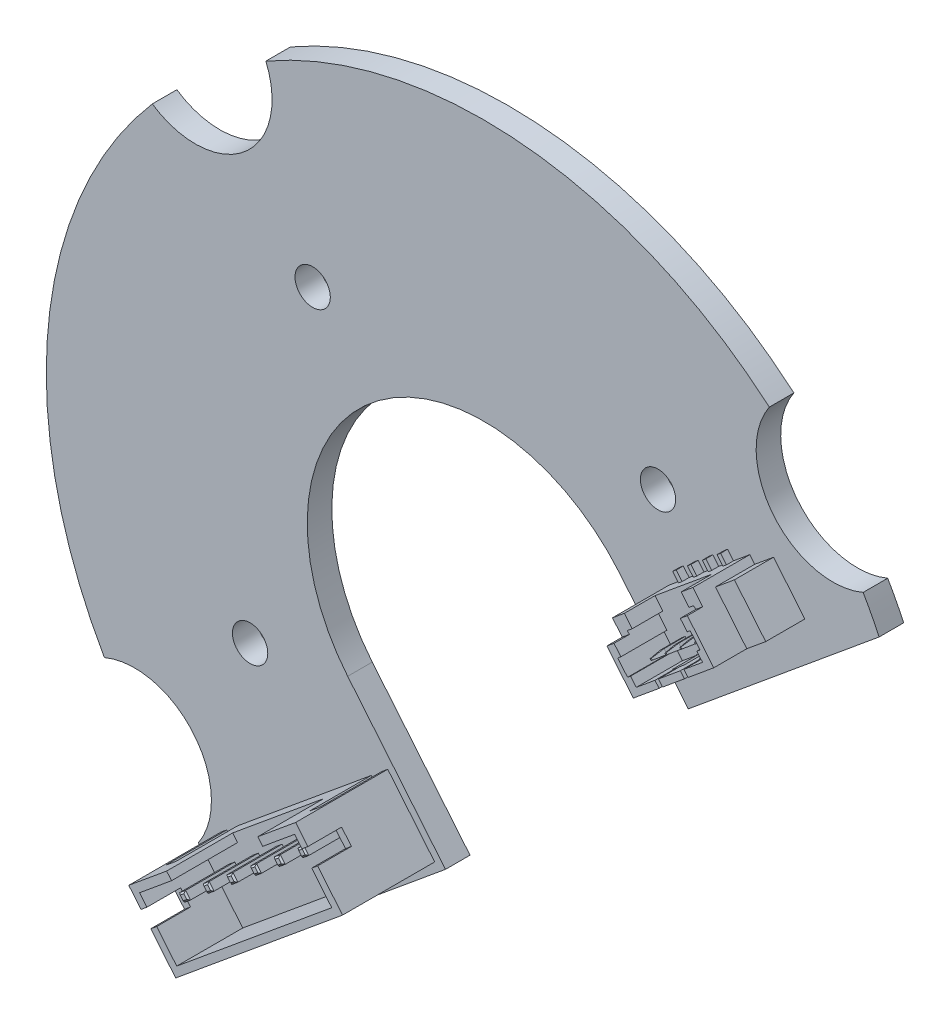
SolidWorks part; units mm, degrees
ref_plane "前视基准面" through (0, 0, 0) normal (0, 0, 1) x (1, 0, 0)
ref_plane "上视基准面" through (0, 0, 0) normal (0, 1, 0) x (1, 0, 0)
ref_plane "右视基准面" through (0, 0, 0) normal (1, 0, 0) x (0, 0, -1)
sketch "草图2" plane through (0, 0, 0) normal (0, 0, 1) x (1, 0, 0)
  line L0 (-14.2036, -24.7084) -> (-2.4954, -15.0341)
  line L1 (-8.8652, -7.3252) -> (-2.4954, -15.0341)
  line L2 (8.8652, 7.3252) -> (13.324, 1.929)
  line L3 (25.756, 12.2015) -> (13.324, 1.929)
  arc A0 (-18.6004, -21.5934) -> (-14.2036, -24.7084) centre (0, 0) ccw
  arc A1 (-21.5934, 18.6004) -> (-14.196, 24.7128) centre (-18.7908, 22.7411) ccw
  arc A2 (-18.6004, -21.5934) -> (-24.7128, -14.196) centre (-22.7411, -18.7908) ccw
  arc A3 (18.6004, 21.5934) -> (24.7128, 14.196) centre (22.7411, 18.7908) ccw
  arc A4 (8.8652, 7.3252) -> (-8.8652, -7.3252) centre (0, 0) ccw
  arc A5 (25.756, 12.2015) -> (24.7128, 14.196) centre (0, 0) ccw
  arc A6 (-21.5934, 18.6004) -> (-24.7128, -14.196) centre (0, 0) ccw
  arc A7 (18.6004, 21.5934) -> (-14.196, 24.7128) centre (0, 0) ccw
  dimension "D1" = 57
  dimension "D2" = 10
  dimension "D3" = 10
  dimension "D4" = 10
  dimension "D5" = 23
  dimension "D6" = 10
  dimension "D7" = 7
extrude "凸台-拉伸1" add sketch "草图2" along normal blind 1.6
sketch "草图3" plane through (0, 0, 1.6) normal (0, 0, 1) x (1, 0, 0)
  line L0 (-6.2568, -11.2669) -> (-3.1994, -14.9671)
  line L1 (-3.1994, -14.9671) -> (-14.0688, -23.9484)
  line L2 (-14.0688, -23.9484) -> (-17.1263, -20.2482)
  line L3 (-17.1263, -20.2482) -> (-6.2568, -11.2669)
  line L6 (-2.4954, -15.0341) -> (-8.8652, -7.3252) construction
  line L8 (-14.2036, -24.7084) -> (-2.4954, -15.0341) construction
  dimension "D1" = 14.1
  dimension "D2" = 4.8
  dimension "D3" = 0.5
  dimension "D4" = 0.5
extrude "凸台-拉伸2" add sketch "草图3" along normal blind 6
sketch "草图4" plane through (0, 0, 7.6) normal (0, 0, 1) x (1, 0, 0)
  line L0 (-6.3238, -11.9708) -> (-3.9033, -14.9001)
  line L1 (-3.9033, -14.9001) -> (-14.0019, -23.2445)
  line L2 (-14.0019, -23.2445) -> (-16.4224, -20.3152)
  line L3 (-16.4224, -20.3152) -> (-14.341, -18.5953)
  line L4 (-3.1994, -14.9671) -> (-6.2568, -11.2669) construction
  line L5 (-17.1263, -20.2482) -> (-14.0688, -23.9484) construction
  line L6 (-6.2568, -11.2669) -> (-17.1263, -20.2482) construction
  line L7 (-14.0688, -23.9484) -> (-3.1994, -14.9671) construction
  line L8 (-7.2854, -21.09) -> (-12.9337, -14.2542) construction
  line L9 (-8.4029, -13.6887) -> (-8.7214, -13.3033)
  line L10 (-8.7214, -13.3033) -> (-14.6595, -18.2099)
  line L11 (-14.6595, -18.2099) -> (-14.341, -18.5953)
  line L12 (-8.4029, -13.6887) -> (-6.3238, -11.9708)
  dimension "D1" = 0.5
  dimension "D2" = 0.5
  dimension "D3" = 0.5
  dimension "D4" = 0.5
  dimension "D5" = 3.853
  dimension "D6" = 3.85
extrude "切除-拉伸1" cut sketch "草图4" against normal offset from surface (4.3 mm away) 1.7 up to face at (-1.9351, 2.4515, 1.6)
sketch "草图5" plane through (0, 0, 7.6) normal (0, 0, 1) x (1, 0, 0)
  line L0 (-5.8461, -12.5489) -> (-5.4606, -12.2305)
  line L1 (-3.9033, -14.9001) -> (-6.3238, -11.9708) construction
  line L2 (-3.1994, -14.9671) -> (-6.2568, -11.2669) construction
  line L3 (-5.4606, -12.2305) -> (-4.8236, -13.0013)
  line L4 (-4.8236, -13.0013) -> (-5.2091, -13.3198)
  line L5 (-5.2091, -13.3198) -> (-5.8461, -12.5489)
  line L6 (-15.9446, -20.8933) -> (-16.3301, -21.2118)
  line L7 (-16.4224, -20.3152) -> (-14.0019, -23.2445) construction
  line L8 (-17.1263, -20.2482) -> (-14.0688, -23.9484) construction
  line L9 (-16.3301, -21.2118) -> (-15.6931, -21.9827)
  line L10 (-15.6931, -21.9827) -> (-15.3077, -21.6642)
  line L11 (-15.3077, -21.6642) -> (-15.9446, -20.8933)
  line L12 (-14.6595, -18.2099) -> (-17.1263, -20.2482) construction
  line L13 (-6.2568, -11.2669) -> (-8.7214, -13.3033) construction
  dimension "D1" = 1.25
  dimension "D2" = 1
  dimension "D3" = 1.25
  dimension "D4" = 1
extrude "切除-拉伸2" cut sketch "草图5" against normal blind 2.2
sketch "草图6" plane through (2.9938, -3.6232, 0) normal (-0.637, 0.7709, 0) x (0.7709, 0.637, 0)
  line L0 (-28.0932, -1.6) -> (-4.798, -1.6) construction
  line L1 (-12.5, -5.6) -> (-13.4, -5.6)
  line L2 (-12.5, -5.6) -> (-12.5, -1.6)
  line L3 (-12.5, -1.6) -> (-13.4, -1.6)
  line L4 (-13.4, -5.6) -> (-13.4, -1.6)
  line L5 (-12, -7.6) -> (-12, -1.6) construction
  line L6 (-24.7, -5.6) -> (-25.6, -5.6)
  line L7 (-24.7, -5.6) -> (-24.7, -1.6)
  line L8 (-24.7, -1.6) -> (-25.6, -1.6)
  line L9 (-25.6, -5.6) -> (-25.6, -1.6)
  line L10 (-26.1, -7.6) -> (-26.1, -1.6) construction
  dimension "D1" = 0.5
  dimension "D2" = 0.5
  dimension "D3" = 0.9
  dimension "D4" = 0.9
  dimension "D5" = 4
  dimension "D6" = 4
extrude "切除-拉伸3" cut sketch "草图6" against normal blind 0.5
sketch "草图7" plane through (0, 0, 3.3) normal (0, 0, 1) x (1, 0, 0)
  line L0 (-6.8164, -13.4156) -> (-6.4979, -13.801)
  line L1 (-6.4979, -13.801) -> (-6.8833, -14.1195)
  line L2 (-6.8833, -14.1195) -> (-7.2018, -13.734)
  line L3 (-7.2018, -13.734) -> (-6.8164, -13.4156)
  line L5 (-6.2568, -11.2669) -> (-8.7214, -13.3033) construction
  line L6 (-3.1994, -14.9671) -> (-4.8236, -13.0013) construction
  line L7 (-8.4251, -15.3934) -> (-8.7436, -15.008)
  line L8 (-8.7436, -15.008) -> (-8.3581, -14.6895)
  line L9 (-8.3581, -14.6895) -> (-8.0396, -15.075)
  line L10 (-8.0396, -15.075) -> (-8.4251, -15.3934)
  line L11 (-9.9669, -16.6674) -> (-10.2853, -16.2819)
  line L12 (-10.2853, -16.2819) -> (-9.8999, -15.9635)
  line L13 (-9.8999, -15.9635) -> (-9.5814, -16.3489)
  line L14 (-9.5814, -16.3489) -> (-9.9669, -16.6674)
  line L15 (-11.5086, -17.9413) -> (-11.8271, -17.5559)
  line L16 (-11.8271, -17.5559) -> (-11.4417, -17.2374)
  line L17 (-11.4417, -17.2374) -> (-11.1232, -17.6229)
  line L18 (-11.1232, -17.6229) -> (-11.5086, -17.9413)
  line L19 (-13.0504, -19.2153) -> (-13.3689, -18.8298)
  line L20 (-13.3689, -18.8298) -> (-12.9834, -18.5114)
  line L21 (-12.9834, -18.5114) -> (-12.6649, -18.8968)
  line L22 (-12.6649, -18.8968) -> (-13.0504, -19.2153)
  line L23 (-14.5922, -20.4892) -> (-14.9106, -20.1038)
  line L24 (-14.9106, -20.1038) -> (-14.5252, -19.7853)
  line L25 (-14.5252, -19.7853) -> (-14.2067, -20.1708)
  line L26 (-14.2067, -20.1708) -> (-14.5922, -20.4892)
  dimension "D1" = 1.8
  dimension "D2" = 0.5
  dimension "D3" = 0.5
  dimension "D4" = 2.3
  dimension "D5" = 6
extrude "凸台-拉伸3" add sketch "草图7" along normal blind 3.3
extrude "凸台-拉伸4" add sketch "草图7<3>" against normal offset from surface (4.4 mm away) 2.7 up to face at (-1.9351, 2.4515, 1.6)
sketch "草图7<3>" plane through (0, 0, 3.3) normal (0, 0, 1) x (1, 0, 0) same geometry as "草图7"
chamfer "倒角1" distance 0.1 angle 45 24 edges at (-14.3994, -20.33, 6.6) (-14.7514, -20.2965, 6.6) (-14.7179, -19.9446, 6.6) (-14.366, -19.978, 6.6) (-12.8577, -19.056, 6.6) (-13.2096, -19.0226, 6.6) (-13.1762, -18.6706, 6.6) (-12.8242, -18.7041, 6.6) (-11.3159, -17.7821, 6.6) (-11.6679, -17.7486, 6.6) (-11.6344, -17.3967, 6.6) (-11.2824, -17.4301, 6.6) (-9.7741, -16.5081, 6.6) (-10.1261, -16.4747, 6.6) (-10.0926, -16.1227, 6.6) (-9.7407, -16.1562, 6.6) (-6.6571, -13.6083, 6.6) (-6.6906, -13.9602, 6.6) (-7.0426, -13.9268, 6.6) (-7.0091, -13.5748, 6.6) (-8.2324, -15.2342, 6.6) (-8.5843, -15.2007, 6.6) (-8.5508, -14.8488, 6.6) (-8.1989, -14.8822, 6.6)
chamfer "倒角2" distance 0.1 angle 45 24 edges at (-14.7179, -19.9446, -1.1) (-14.7514, -20.2965, -1.1) (-14.3994, -20.33, -1.1) (-14.366, -19.978, -1.1) (-13.1762, -18.6706, -1.1) (-13.2096, -19.0226, -1.1) (-12.8577, -19.056, -1.1) (-12.8242, -18.7041, -1.1) (-11.6344, -17.3967, -1.1) (-11.6679, -17.7486, -1.1) (-11.3159, -17.7821, -1.1) (-11.2824, -17.4301, -1.1) (-10.0926, -16.1227, -1.1) (-10.1261, -16.4747, -1.1) (-9.7741, -16.5081, -1.1) (-9.7407, -16.1562, -1.1) (-8.5508, -14.8488, -1.1) (-8.5843, -15.2007, -1.1) (-8.2324, -15.2342, -1.1) (-8.1989, -14.8822, -1.1) (-7.0426, -13.9268, -1.1) (-6.6906, -13.9602, -1.1) (-6.6571, -13.6083, -1.1) (-7.0091, -13.5748, -1.1)
sketch "草图8" plane through (0, 0, 0) normal (0, 0, -1) x (-1, 0, 0)
  line L0 (28.3719, 2.6986) -> (0, 0) construction
  line L1 (27.8185, 4.1494) -> (28.102, 1.1695)
  arc A2 (27.8185, 4.1494) -> (28.102, 1.1695) centre (25.3719, 2.4133) ccw
  arc A3 (24.7128, -14.196) -> (21.5934, 18.6004) centre (0, 0) ccw construction
  point P4 (22.3854, 2.1292)
  dimension "D1" = 6
  dimension "D2" = 3
  dimension "D3" = 5.6
extrude "凸台-拉伸5" add sketch "草图8" along normal blind 1
sketch "草图9" plane through (0, 0, -1) normal (0, 0, -1) x (-1, 0, 0)
  circle A0 centre (25.3719, 2.4133) radius 2.5
  arc A2 (27.8185, 4.1494) -> (28.102, 1.1695) centre (25.3719, 2.4133) ccw construction
  dimension "D1" = 5
extrude "凸台-拉伸6" add sketch "草图9" along normal blind 7.5
fillet "圆角2" radius 2.5 1 edges at (-27.8719, 2.4133, -8.5)
sketch "草图10" plane through (0, 0, 1.6) normal (0, 0, 1) x (1, 0, 0)
  line L0 (-15.6059, 18.8867) -> (0, 0) construction
  line L1 (0, 0) -> (11.3499, 13.3203) construction
  line L2 (-15.2212, -8.6351) -> (0, 0) construction
  circle A0 centre (0, 0) radius 17.5 construction
  circle A1 centre (11.3499, 13.3203) radius 1.15
  circle A2 centre (-11.1471, 13.4905) radius 1.15
  circle A3 centre (-15.2212, -8.6351) radius 1.15
  arc A4 (-21.5934, 18.6004) -> (-14.196, 24.7128) centre (-18.7908, 22.7411) ccw construction
  dimension "D1" = 2.3
  dimension "D2" = 2.3
  dimension "D3" = 2.3
  dimension "D4" = 80
  dimension "D5" = 80
extrude "切除-拉伸4" cut sketch "草图10" against normal blind 2.4
sketch "草图11" plane through (0, 0, 1.6) normal (0, 0, 1) x (1, 0, 0)
  line L0 (10.8496, 7.2785) -> (18.5584, 13.6483)
  line L1 (18.5584, 13.6483) -> (20.9152, 10.796)
  line L2 (20.9152, 10.796) -> (13.2064, 4.4263)
  line L3 (13.2064, 4.4263) -> (10.8496, 7.2785)
  line L4 (8.8652, 7.3252) -> (13.324, 1.929) construction
  line L5 (13.324, 1.929) -> (25.756, 12.2015) construction
  dimension "D1" = 10
  dimension "D2" = 3.7
  dimension "D3" = 1.5
  dimension "D4" = 2
extrude "凸台-拉伸7" add sketch "草图11" along normal blind 4.7
sketch "草图12" plane through (0, 0, 6.3) normal (0, 0, 1) x (1, 0, 0)
  line L0 (17.325, 12.6291) -> (19.6818, 9.7768)
  line L1 (18.5584, 13.6483) -> (10.8496, 7.2785) construction
  line L2 (13.2064, 4.4263) -> (20.9152, 10.796) construction
  line L3 (19.6818, 9.7768) -> (20.9152, 10.796)
  line L4 (20.9152, 10.796) -> (18.5584, 13.6483)
  line L5 (20.9152, 10.796) -> (18.5584, 13.6483) construction
  line L6 (18.5584, 13.6483) -> (17.325, 12.6291)
  line L7 (10.8496, 7.2785) -> (12.083, 8.2977)
  line L8 (10.8496, 7.2785) -> (13.2064, 4.4263) construction
  line L9 (12.083, 8.2977) -> (14.4398, 5.4454)
  line L10 (14.4398, 5.4454) -> (13.2064, 4.4263)
  line L11 (13.2064, 4.4263) -> (10.8496, 7.2785)
  dimension "D1" = 1.6
  dimension "D2" = 1.6
extrude "切除-拉伸5" cut sketch "草图12" against normal blind 2.15
sketch "草图13" plane through (0, 0, 4.15) normal (0, 0, 1) x (1, 0, 0)
  line L0 (18.5584, 13.6483) -> (17.325, 12.6291)
  line L1 (20.9152, 10.796) -> (18.5584, 13.6483) construction
  line L2 (18.5584, 13.6483) -> (17.325, 12.6291) construction
  line L3 (17.325, 12.6291) -> (19.6818, 9.7768) construction
  line L4 (17.325, 12.6291) -> (17.6435, 12.2437)
  line L5 (17.6435, 12.2437) -> (18.8769, 13.2628)
  line L6 (18.8769, 13.2628) -> (18.5584, 13.6483)
  line L7 (12.083, 8.2977) -> (10.8496, 7.2785)
  line L8 (12.083, 8.2977) -> (10.8496, 7.2785) construction
  line L9 (14.4398, 5.4454) -> (12.083, 8.2977) construction
  line L10 (10.8496, 7.2785) -> (11.1681, 6.8931)
  line L11 (10.8496, 7.2785) -> (13.2064, 4.4263) construction
  line L12 (11.1681, 6.8931) -> (12.4015, 7.9122)
  line L13 (12.4015, 7.9122) -> (12.083, 8.2977)
  dimension "D1" = 0.5
  dimension "D2" = 0.5
extrude "切除-拉伸6" cut sketch "草图13" against normal up to surface (2.55 mm away) up to face at (12.4999, 13.3203, 1.6)
sketch "草图14" plane through (0, 0, 6.3) normal (0, 0, 1) x (1, 0, 0)
  line L0 (16.5541, 11.9921) -> (17.0637, 11.3754)
  line L1 (17.325, 12.6291) -> (12.083, 8.2977) construction
  line L2 (17.0637, 11.3754) -> (17.372, 11.6302)
  line L3 (17.372, 11.6302) -> (17.9453, 10.9364)
  line L4 (17.9453, 10.9364) -> (18.1458, 11.102)
  line L5 (18.1458, 11.102) -> (18.7827, 10.3312)
  line L6 (18.7827, 10.3312) -> (18.5823, 10.1655)
  line L7 (18.5823, 10.1655) -> (18.9517, 9.7184)
  line L8 (18.9517, 9.7184) -> (14.6348, 6.1514)
  line L9 (14.6348, 6.1514) -> (14.2653, 6.5985)
  line L10 (14.2653, 6.5985) -> (14.0649, 6.4329)
  line L11 (14.0649, 6.4329) -> (13.4279, 7.2038)
  line L12 (13.4279, 7.2038) -> (13.6284, 7.3694)
  line L13 (13.6284, 7.3694) -> (13.0551, 8.0632)
  line L14 (13.0551, 8.0632) -> (13.3634, 8.3179)
  line L15 (13.3634, 8.3179) -> (12.8539, 8.9347)
  line L16 (12.8539, 8.9347) -> (16.5541, 11.9921)
  line L17 (14.4398, 5.4454) -> (19.6818, 9.7768) construction
  line L18 (17.325, 12.6291) -> (19.6818, 9.7768) construction
  line L19 (14.4398, 5.4454) -> (12.083, 8.2977) construction
  dimension "D1" = 0.42
  dimension "D2" = 0.34
  dimension "D3" = 0.34
  dimension "D4" = 0.6
  dimension "D5" = 0.6
  dimension "D6" = 0.6
  dimension "D7" = 0.6
  dimension "D8" = 1
  dimension "D9" = 1
  dimension "D10" = 1
  dimension "D11" = 1
  dimension "D12" = 0.8
  dimension "D13" = 0.8
  dimension "D14" = 1
  dimension "D15" = 1
extrude "切除-拉伸7" cut sketch "草图14" against normal blind 3
sketch "草图15" plane through (0, 0, 6.3) normal (0, 0, 1) x (1, 0, 0)
  line L0 (12.083, 8.2977) -> (17.325, 12.6291)
  line L1 (14.4398, 5.4454) -> (12.083, 8.2977) construction
  line L2 (17.325, 12.6291) -> (19.6818, 9.7768) construction
  line L3 (17.325, 12.6291) -> (16.5541, 11.9921) construction
  line L4 (17.325, 12.6291) -> (17.962, 11.8582)
  line L5 (17.962, 11.8582) -> (12.72, 7.5268)
  line L6 (12.72, 7.5268) -> (12.083, 8.2977)
  dimension "D1" = 1
extrude "切除-拉伸8" cut sketch "草图15" against normal blind 1
sketch "草图16" plane through (3.1849, -3.8544, 0) normal (0.637, -0.7709, 0) x (0.7709, 0.637, 0)
  line L0 (11.5, 1.6) -> (27.627, 1.6) construction
  line L1 (16.43, 4.9) -> (16.78, 4.9)
  line L2 (16.43, 4.9) -> (16.43, 1.6)
  line L3 (16.43, 1.6) -> (17.43, 1.6)
  line L4 (17.43, 4.9) -> (17.43, 1.6)
  line L5 (14.6, 6.3) -> (21.4, 6.3) construction
  line L6 (18.57, 4.9) -> (18.92, 4.9)
  line L7 (18.57, 4.9) -> (18.57, 1.6)
  line L8 (18.57, 1.6) -> (19.57, 1.6)
  line L9 (19.57, 4.9) -> (19.57, 1.6)
  line L11 (16.78, 4.9) -> (16.78, 6.3)
  line L12 (16.78, 6.3) -> (17.08, 6.3)
  line L13 (17.08, 4.9) -> (17.08, 6.3)
  line L16 (18.92, 4.9) -> (18.92, 6.3)
  line L17 (18.92, 6.3) -> (19.22, 6.3)
  line L18 (19.22, 4.9) -> (19.22, 6.3)
  line L20 (14.6, 4.15) -> (14.6, 6.3) construction
  line L23 (17.08, 4.9) -> (17.43, 4.9)
  line L24 (19.22, 4.9) -> (19.57, 4.9)
  dimension "D1" = 1
  dimension "D2" = 1
  dimension "D3" = 0.3
  dimension "D4" = 0.3
  dimension "D5" = 0.35
  dimension "D6" = 0.35
  dimension "D7" = 1.14
  dimension "D8" = 1.83
  dimension "D9" = 3.3
  dimension "D10" = 3.3
extrude "切除-拉伸9" cut sketch "草图16" against normal blind 0.45
sketch "草图17" plane through (0, 0, 3.3) normal (0, 0, 1) x (1, 0, 0)
  line L0 (17.7148, 10.0065) -> (17.9059, 9.7753)
  line L1 (17.9059, 9.7753) -> (17.6746, 9.5842)
  line L2 (17.6746, 9.5842) -> (17.4836, 9.8155)
  line L3 (17.4836, 9.8155) -> (17.7148, 10.0065)
  line L4 (18.0013, 8.3882) -> (19.6818, 9.7768) construction
  line L5 (17.962, 11.8582) -> (19.6818, 9.7768) construction
  line L6 (16.711, 8.788) -> (16.5199, 9.0192)
  line L7 (16.5199, 9.0192) -> (16.7512, 9.2103)
  line L8 (16.7512, 9.2103) -> (16.9423, 8.9791)
  line L9 (16.9423, 8.9791) -> (16.711, 8.788)
  line L10 (15.7474, 7.9918) -> (15.5563, 8.223)
  line L11 (15.5563, 8.223) -> (15.7876, 8.4141)
  line L12 (15.7876, 8.4141) -> (15.9787, 8.1828)
  line L13 (15.9787, 8.1828) -> (15.7474, 7.9918)
  line L14 (14.7838, 7.1955) -> (14.5927, 7.4268)
  line L15 (14.5927, 7.4268) -> (14.824, 7.6179)
  line L16 (14.824, 7.6179) -> (15.0151, 7.3866)
  line L17 (15.0151, 7.3866) -> (14.7838, 7.1955)
  dimension "D1" = 0.3
  dimension "D2" = 0.3
  dimension "D3" = 1.43
  dimension "D4" = 1.67
  dimension "D5" = 4
extrude "凸台-拉伸8" add sketch "草图17" along normal offset from surface (2.2 mm away) 0.8 up to face at (18.3286, 10.2465, 6.3)
chamfer "倒角3" distance 0.1 angle 83 16 edges at (14.9195, 7.5023, 5.5) (14.8995, 7.2911, 5.5) (14.6883, 7.3112, 5.5) (14.7084, 7.5223, 5.5) (15.8832, 8.2985, 5.5) (15.8631, 8.0873, 5.5) (15.6519, 8.1074, 5.5) (15.672, 8.3186, 5.5) (17.5992, 9.911, 5.5) (17.8104, 9.8909, 5.5) (17.7903, 9.6797, 5.5) (17.5791, 9.6998, 5.5) (16.8468, 9.0947, 5.5) (16.8267, 8.8835, 5.5) (16.6155, 8.9036, 5.5) (16.6356, 9.1148, 5.5) first distance on face at (14.8039, 7.4067, 5.5) first distance on face at (15.7675, 8.2029, 5.5) first distance on face at (17.6947, 9.7954, 5.5) first distance on face at (16.7311, 8.9992, 5.5)
sketch "草图18" plane through (0, 0, 1.6) normal (0, 0, 1) x (1, 0, 0)
  line L0 (13.1468, 9.1767) -> (12.7646, 9.6392)
  line L1 (16.5541, 11.9921) -> (12.8539, 8.9347) construction
  line L2 (12.7646, 9.6392) -> (12.9959, 9.8303)
  line L3 (12.9959, 9.8303) -> (13.3781, 9.3678)
  line L4 (13.3781, 9.3678) -> (13.1468, 9.1767)
  line L5 (14.7838, 7.1955) -> (14.5927, 7.4268) construction
  line L6 (14.824, 7.6179) -> (15.0151, 7.3866) construction
  line L7 (13.7282, 10.4355) -> (13.9595, 10.6265)
  line L8 (14.1104, 9.9729) -> (13.7282, 10.4355)
  line L9 (13.9595, 10.6265) -> (14.3417, 10.164)
  line L10 (14.3417, 10.164) -> (14.1104, 9.9729)
  line L11 (14.6918, 11.2317) -> (14.9231, 11.4228)
  line L12 (15.074, 10.7691) -> (14.6918, 11.2317)
  line L13 (14.9231, 11.4228) -> (15.3053, 10.9602)
  line L14 (15.3053, 10.9602) -> (15.074, 10.7691)
  line L15 (15.6554, 12.0279) -> (15.8867, 12.219)
  line L16 (16.0376, 11.5654) -> (15.6554, 12.0279)
  line L17 (15.8867, 12.219) -> (16.2689, 11.7565)
  line L18 (16.2689, 11.7565) -> (16.0376, 11.5654)
  dimension "D1" = 0.6
  dimension "D2" = 4
extrude "凸台-拉伸9" add sketch "草图18" along normal blind 0.46
sketch "草图19" plane through (0, 0, 1.6) normal (0, 0, 1) x (1, 0, 0)
  circle A0 centre (-11.1471, 13.4905) radius 2
  circle A1 centre (-15.2212, -8.6351) radius 2
  circle A2 centre (11.3499, 13.3203) radius 2
